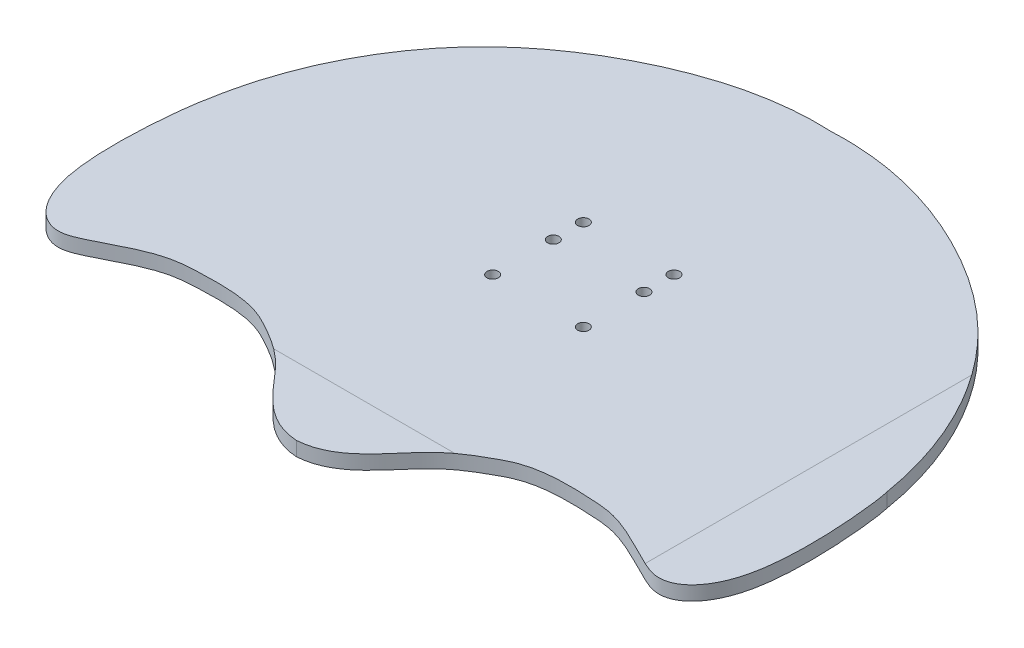
SolidWorks part; units mm, degrees
material "6061-T6 (SS)"
ref_plane "Front Plane" through (0, 0, 0) normal (0, 0, 1) x (1, 0, 0)
ref_plane "Top Plane" through (0, 0, 0) normal (0, 1, 0) x (1, 0, 0)
ref_plane "Right Plane" through (0, 0, 0) normal (1, 0, 0) x (0, 0, -1)
sketch "Sketch3" plane through (0, 0, 0) normal (0, 1, 0) x (1, 0, 0)
  line L0 (0, 0) -> (0, 159.1899) construction
  line L1 (0, 0) -> (0, -140.5301) construction
  line L2 (0, 0) -> (-190.5, 0) construction
  line L3 (0, 0) -> (190.5, 0) construction
  spline S0 degree 3 poles (-190.5, 0) (-184.3927, 37.537) (-157.2613, 93.9641) (-82.3875, 146.6227) (-31.3114, 160.7999) (0, 159.1899) knots 0 0 0 0 0.424401 0.65637 1 1 1 1
  spline S1 degree 3 poles (-190.5, 0) (-192.064, -4.9635) (-201.9672, -83.3146) (-174.6966, -109.29) (-151.6301, -100.568) (-131.4108, -87.7198) (-96.8436, -85.3754) (-78.6925, -86.2588) (-58.8335, -96.8794) (-37.3059, -109.9358) (-21.3496, -139.1148) (0, -140.5301) knots 0 0 0 0 0.166997 0.292321 0.319633 0.426735 0.458914 0.609242 0.64191 0.766802 1 1 1 1
  spline S2 degree 3 poles (190.5, 0) (192.064, -4.9635) (201.9672, -83.3146) (174.6966, -109.29) (151.6301, -100.568) (131.4108, -87.7198) (96.8436, -85.3754) (78.6925, -86.2588) (58.8335, -96.8794) (37.3059, -109.9358) (21.3496, -139.1148) (0, -140.5301) knots 0 0 0 0 0.166997 0.292321 0.319633 0.426735 0.458914 0.609242 0.64191 0.766802 1 1 1 1
  spline S3 degree 3 poles (190.5, 0) (184.3927, 37.537) (157.2613, 93.9641) (82.3875, 146.6227) (31.3114, 160.7999) (0, 159.1899) knots 0 0 0 0 0.424401 0.65637 1 1 1 1
  dimension "D1" = 381
  dimension "D2" = 299.72
  dimension "D3" = 159.1899
  dimension "D4" = 86.8953
  dimension "D5" = 104.4979
  dimension "D6" = 29.1616
  dimension "D7" = 92.2742
  dimension "D8" = 108.411
  dimension "D9" = 67.4883
  dimension "D10" = 43.7314
  dimension "D11" = 117.6915
  dimension "D12" = 162.2568
  dimension "D13" = 89.4522
  dimension "D14" = 140.1036
  dimension "D15" = 175.0666
  dimension "D16" = 50.2669
  dimension "D17" = 101.3666
  dimension "D18" = 138.1225
  dimension "D19" = 155.1557
  dimension "D20" = 192.0074
  dimension "D21" = 193.9268
  dimension "D23" = 76.6666
extrude "Boss-Extrude1" add sketch "Sketch3" along normal blind 7.9502 from surface starting at plane "Top Plane"
sketch "Sketch5" plane through (0, 0, 0) normal (0, -1, 0) x (1, 0, 0)
  line L0 (0, 0) -> (0, -20.32) construction
  line L1 (25.4, -45.72) -> (-25.4, -45.72)
  line L2 (25.4, -45.72) -> (25.4, 5.08)
  line L3 (25.4, 5.08) -> (-25.4, 5.08)
  line L4 (-25.4, -45.72) -> (-25.4, 5.08)
  line L5 (25.4, -45.72) -> (-25.4, 5.08) construction
  line L6 (25.4, 5.08) -> (-25.4, -45.72) construction
  line L7 (-25.4, -45.72) -> (-25.4, -28.8925)
  line L8 (-25.4, -28.8925) -> (25.4, -28.8925) construction
  point P0 (0, -20.32)
  point P3 (0, -20.32)
  dimension "D2" = 50.8
  dimension "D3" = 50.8
  dimension "D4" = 16.8275
hole_wizard "1/4 (0.25) Diameter Hole1" positions "Sketch6" profile "Sketch7" hole size "1/4" standard "ANSI Inch" end condition through all
sketch "Sketch6" plane through (0, 0, 0) normal (0, -1, 0) x (-1, 0, 0)
  point P0 (-25.4, 45.72)
  point P3 (25.4, 45.72)
  point P6 (25.4, -5.08)
  point P9 (-25.4, -5.08)
  point P12 (-25.4, 28.8925)
  point P15 (25.4, 28.8925)
sketch "Sketch7" plane through (25.4, 0, -45.72) normal (1, 0, 0) x (0, 0, -1)
  line L0 (0, 0) -> (0, 7.9502)
  line L1 (0, 7.9502) -> (3.175, 7.9502)
  line L2 (3.175, 7.9502) -> (3.175, 0)
  line L5 (3.175, 0) -> (0, 0)
  line L11 (0, -6.35) -> (0, 107.95) construction
  dimension "Thru Hole Dia." = 6.35
  dimension "Thru Hole Depth" = 7.9502
sketch "Sketch9" plane through (0, 7.9502, 0) normal (0, 1, 0) x (1, 0, 0)
  line L0 (157.5201, -102.5466) -> (157.5201, 80.5195)
  line L1 (-50.7649, -102.4301) -> (50.7649, -102.4301)
  spline S0 degree 3 poles (0, -140.5301) (21.3496, -139.1148) (37.3059, -109.9358) (58.8335, -96.8794) (78.6925, -86.2588) (96.8436, -85.3754) (131.4108, -87.7198) (151.6301, -100.568) (174.6966, -109.29) (201.9672, -83.3146) (192.064, -4.9635) (190.5, 0) knots 0 0 0 0 0.233198 0.35809 0.390758 0.541086 0.573265 0.680367 0.707679 0.833003 1 1 1 1 construction
  spline S1 degree 3 poles (190.5, 0) (184.3927, 37.537) (157.2613, 93.9641) (82.3875, 146.6227) (31.3114, 160.7999) (0, 159.1899) knots 0 0 0 0 0.424401 0.65637 1 1 1 1 construction
  spline S2 degree 3 poles (-190.5, 0) (-192.064, -4.9635) (-201.9672, -83.3146) (-174.6966, -109.29) (-151.6301, -100.568) (-131.4108, -87.7198) (-96.8436, -85.3754) (-78.6925, -86.2588) (-58.8335, -96.8794) (-37.3059, -109.9358) (-21.3496, -139.1148) (0, -140.5301) knots 0 0 0 0 0.166997 0.292321 0.319633 0.426735 0.458914 0.609242 0.64191 0.766802 1 1 1 1 construction
  dimension "D1" = 38.1
split line "Split Line1"
equation "\"Plate thickness\"=0.313"
equation "\"D1@Boss-Extrude1\"=\"Plate thickness\""
equation "\"Bracket Alignment\"= .80"
equation "\"D1@Sketch5\"=\"Bracket Alignment\""
